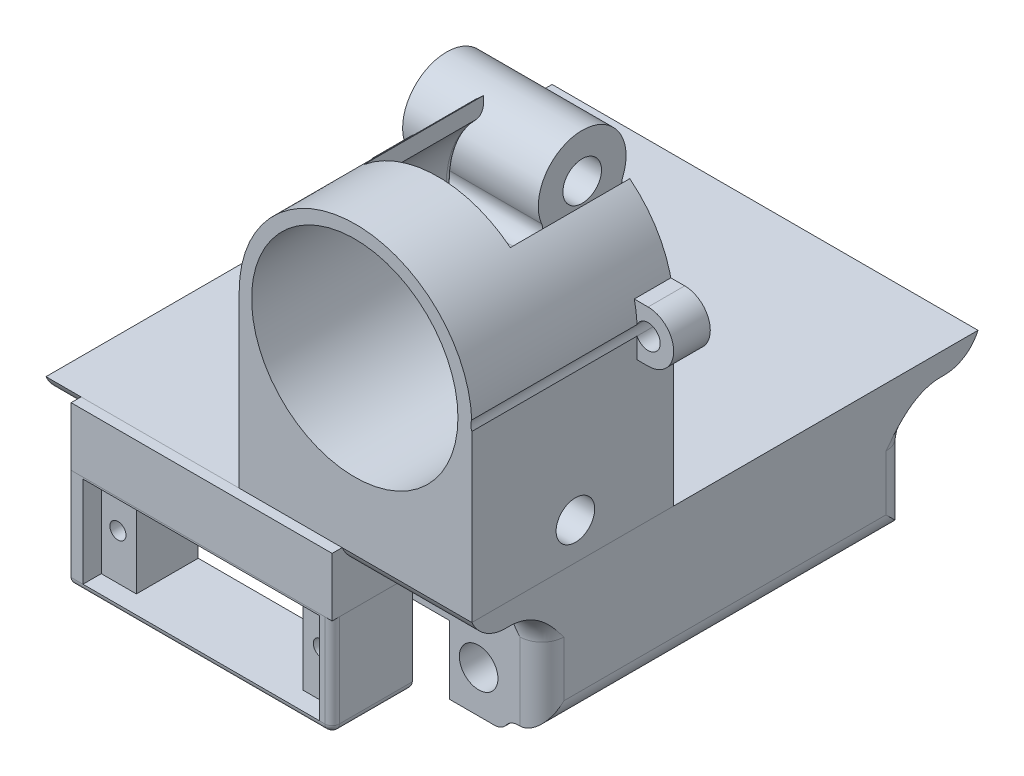
SolidWorks part; units mm, degrees
material "PLA"
ref_plane "Front Plane" through (0, 0, 0) normal (0, 0, 1) x (1, 0, 0)
ref_plane "Top Plane" through (0, 0, 0) normal (0, 1, 0) x (1, 0, 0)
ref_plane "Right Plane" through (0, 0, 0) normal (1, 0, 0) x (0, 0, -1)
ref_plane "Plane69" through (0, 0, 32) normal (0, 0, -1) x (-1, 0, 0)
sketch "Sketch1047" plane through (0, 0, 32) normal (0, 0, -1) x (-1, 0, 0)
  line L0 (-99.3586, 143.8623) -> (-99.3586, 121.2496)
  line L1 (-99.3586, 121.2496) -> (-67.5672, 121.2496)
  line L2 (-67.5672, 121.2496) -> (-67.5672, 144.5496)
  arc A0 (-67.5672, 144.5496) -> (-99.3451, 145.2066) centre (-83.4629, 144.5496) ccw
  arc A1 (-99.3451, 145.2066) -> (-99.3586, 143.8623) centre (-100.8586, 144.5496) cw
extrude "Boss-Extrude62" add sketch "Sketch1047" against normal blind 27.5826 separate body
sketch "Sketch1048" plane through (0, 0, 32) normal (0, 0, -1) x (-1, 0, 0)
  line L0 (-93.3586, 156.9894) -> (-93.3586, 154.49)
  line L1 (-73.3586, 154.49) -> (-73.3586, 156.8206)
  arc A0 (-73.3586, 156.8206) -> (-93.3586, 156.9894) centre (-83.4629, 144.5496) ccw
  arc A1 (-93.3586, 154.49) -> (-73.3586, 154.49) centre (-83.3586, 144.5496) cw
extrude "Cut-Extrude69" cut sketch "Sketch1048" against normal blind 16.3164
ref_plane "Plane70" through (0, 144.5496, 0) normal (0, 1, 0) x (1, 0, 0)
sketch "Sketch1053" plane through (0, 144.5496, 0) normal (0, 1, 0) x (1, 0, 0)
  line L0 (97.4586, -32) -> (83.3586, -32)
  line L1 (83.3586, -32) -> (83.3586, -59.5826)
  line L2 (83.3586, -59.5826) -> (97.4586, -59.5826)
  line L3 (97.4586, -59.5826) -> (97.4586, -32)
  line L4 (83.3586, -32) -> (83.3586, -59.5826) construction
revolve "Cut-Revolve3" cut sketch "Sketch1053" angle 360 about L1 reverse direction yes
hole_wizard "Hole28" positions "Sketch1055" profile "Sketch1054" legacy
sketch "Sketch1055" plane through (99.3586, 0, 0) normal (1, 0, 0) x (0, 0, -1)
  point P0 (-45.4327, 126.3054)
sketch "Sketch1054" plane through (99.3586, 126.3054, 45.4327) normal (0, 1, 0) x (0, 0, -1)
  line L0 (0, 0) -> (0, 31.7914)
  line L1 (0, 31.7914) -> (2.6375, 31.7914)
  line L2 (2.6375, 31.7914) -> (2.6375, 0)
  line L3 (2.6375, 0) -> (0, 0)
  line L4 (0, 110) -> (0, -10) construction
  dimension "Diameter" = 5.275
  dimension "Depth" = 31.7914
fillet "Fillet36" radius 1 1 edges at (83.3586, 130.4496, 32) tangent propagation no
ref_plane "Plane71" through (96.091, 0, 0) normal (1, 0, 0) x (0, 0, -1)
sketch "Sketch1061" plane through (96.091, 0, 0) normal (1, 0, 0) x (0, 0, -1)
  line L0 (-55, 118.2496) -> (5, 118.2496)
  line L1 (9.5826, 121.2496) -> (-59.5826, 121.2496)
  arc A0 (-59.5826, 121.2496) -> (-55, 118.2496) centre (-55, 123.2496) ccw
  arc A1 (5, 118.2496) -> (9.5826, 121.2496) centre (5, 123.2496) ccw
extrude "Boss-Extrude63" add sketch "Sketch1061" against normal blind 3.2327 separate body
ref_plane "Plane72" through (0, 0, -5) normal (0, 0, -1) x (-1, 0, 0)
sketch "Sketch1068" plane through (0, 0, -5) normal (0, 0, -1) x (-1, 0, 0)
  line L0 (-92.8583, 101.0527) -> (-92.8583, 118.2496)
  line L1 (-92.8583, 118.2496) -> (-96.091, 118.2496)
  line L2 (-96.091, 118.2496) -> (-96.091, 102.6969)
  arc A0 (-96.091, 102.6969) -> (-94.4746, 101.8748) centre (-96.091, 100.6969) cw
  arc A1 (-94.4746, 101.8748) -> (-92.8583, 101.0527) centre (-92.8583, 103.0527) ccw
extrude "Boss-Extrude64" add sketch "Sketch1068" against normal blind 60
ref_plane "Plane73" through (92.8583, 0, 0) normal (-1, 0, 0) x (0, 0, 1)
sketch "Sketch1076" plane through (92.8583, 0, 0) normal (-1, 0, 0) x (0, 0, 1)
  line L0 (-5, 101.0527) -> (-5, 118.2496)
  line L1 (-9.5826, 121.2496) -> (59.5826, 121.2496)
  line L2 (55, 118.2496) -> (55, 101.0527)
  line L3 (55, 101.0527) -> (-5, 101.0527)
  arc A0 (-5, 118.2496) -> (-9.5826, 121.2496) centre (-5, 123.2496) cw
  arc A1 (59.5826, 121.2496) -> (55, 118.2496) centre (55, 123.2496) cw
extrude "Boss-Extrude65" add sketch "Sketch1076" along normal blind 51.6948
sketch "Sketch1077" plane through (41.1635, 0, 0) normal (-1, 0, 0) x (0, 0, 1)
  line L0 (55, 110.3759) -> (-5, 110.3759)
  line L1 (-5, 110.3759) -> (-5, 101.0527)
  line L2 (-5, 101.0527) -> (55, 101.0527)
  line L3 (55, 101.0527) -> (55, 110.3759)
extrude "Cut-Extrude70" cut sketch "Sketch1077" against normal blind 45.5365
sketch "Sketch1078" plane through (96.091, 0, 0) normal (1, 0, 0) x (0, 0, -1)
  line L0 (5, 118.2496) -> (5, 102.6969)
  line L1 (5, 102.6969) -> (-55, 102.6969)
  line L2 (-55, 102.6969) -> (-55, 118.2496)
  line L3 (-59.5826, 121.2496) -> (9.5826, 121.2496)
  arc A0 (-55, 118.2496) -> (-59.5826, 121.2496) centre (-55, 123.2496) cw
  arc A1 (9.5826, 121.2496) -> (5, 118.2496) centre (5, 123.2496) cw
extrude "Boss-Extrude66" add sketch "Sketch1078" along normal blind 3.2677
ref_plane "Plane74" through (0, 0, 45) normal (0, 0, 1) x (1, 0, 0)
sketch "Sketch1087" plane through (0, 0, 45) normal (0, 0, 1) x (1, 0, 0)
  line L0 (96.1422, 102.6969) -> (96.1422, 110.3759)
  line L1 (96.1422, 110.3759) -> (86.7, 110.3759)
  line L2 (86.7, 110.3759) -> (86.7, 101.0527)
  line L3 (86.7, 101.0527) -> (92.8583, 101.0527)
  line L4 (96.091, 102.6969) -> (96.1422, 102.6969)
  arc A0 (92.8583, 101.0527) -> (94.4746, 101.8748) centre (92.8583, 103.0527) ccw
  arc A1 (94.4746, 101.8748) -> (96.091, 102.6969) centre (96.091, 100.6969) cw
extrude "Cut-Extrude71" cut sketch "Sketch1087" against normal blind 40
sketch "Sketch1088" plane through (0, 0, 55) normal (0, 0, 1) x (1, 0, 0)
  line L0 (41.1635, 118.2496) -> (41.1635, 110.3759)
  line L1 (41.1635, 110.3759) -> (86.7, 110.3759)
  line L2 (86.7, 110.3759) -> (86.7, 101.0527)
  line L3 (86.7, 101.0527) -> (92.8583, 101.0527)
  line L4 (96.091, 102.6969) -> (99.3586, 102.6969)
  line L5 (99.3586, 102.6969) -> (99.3586, 118.2496)
  line L6 (99.3586, 118.2496) -> (41.1635, 118.2496)
  arc A0 (92.8583, 101.0527) -> (94.4746, 101.8748) centre (92.8583, 103.0527) ccw
  arc A1 (94.4746, 101.8748) -> (96.091, 102.6969) centre (96.091, 100.6969) cw
extrude "Cut-Extrude72" cut sketch "Sketch1088" against normal blind 5
sketch "Sketch1089" plane through (0, 0, -5) normal (0, 0, -1) x (-1, 0, 0)
  line L0 (-86.7, 110.3759) -> (-41.1635, 110.3759)
  line L1 (-41.1635, 110.3759) -> (-41.1635, 118.2496)
  line L2 (-41.1635, 118.2496) -> (-99.3586, 118.2496)
  line L3 (-99.3586, 118.2496) -> (-99.3586, 102.6969)
  line L4 (-99.3586, 102.6969) -> (-96.091, 102.6969)
  line L5 (-92.8583, 101.0527) -> (-86.7, 101.0527)
  line L6 (-86.7, 101.0527) -> (-86.7, 110.3759)
  arc A0 (-96.091, 102.6969) -> (-94.4746, 101.8748) centre (-96.091, 100.6969) cw
  arc A1 (-94.4746, 101.8748) -> (-92.8583, 101.0527) centre (-92.8583, 103.0527) ccw
extrude "Cut-Extrude73" cut sketch "Sketch1089" against normal blind 5
ref_plane "Plane75" through (0, 110.3759, 0) normal (0, -1, 0) x (-1, 0, 0)
sketch "Sketch1099" plane through (0, 110.3759, 0) normal (0, -1, 0) x (-1, 0, 0)
  line L0 (-94.1229, -37) -> (-96.1422, -37)
  line L1 (-96.1422, -37) -> (-96.1422, -13)
  line L2 (-96.1422, -13) -> (-94.1229, -13)
  line L3 (-94.1229, -13) -> (-94.1229, -37)
extrude "Boss-Extrude67" add sketch "Sketch1099" along normal blind 7.679 separate body
sketch "Sketch1110" plane through (0, 110.3759, 0) normal (0, -1, 0) x (-1, 0, 0)
  line L0 (-96.1422, -13) -> (-85.1422, -13)
  line L1 (-85.1422, -13) -> (-85.1422, -5)
  line L2 (-85.1422, -5) -> (-96.1422, -5)
  line L3 (-96.1422, -5) -> (-96.1422, -13)
extrude "Cut-Extrude74" cut sketch "Sketch1110" against normal blind 7.321
sketch "Sketch1111" plane through (0, 110.3759, 0) normal (0, -1, 0) x (1, 0, 0)
  line L0 (96.1422, 37) -> (96.1422, 45)
  line L1 (96.1422, 45) -> (85.1422, 45)
  line L2 (85.1422, 45) -> (85.1422, 37)
  line L3 (85.1422, 37) -> (96.1422, 37)
extrude "Cut-Extrude75" cut sketch "Sketch1111" against normal blind 7.321
ref_plane "Plane76" through (41.1635, 0, 0) normal (-1, 0, 0) x (0, 0, 1)
sketch "Sketch1122" plane through (41.1635, 0, 0) normal (-1, 0, 0) x (0, 0, 1)
  line L0 (-2.5433, 121.2496) -> (12.2435, 121.2496)
  arc A0 (-0.6949, 124.0136) -> (-2.5433, 121.2496) centre (-2.5433, 123.2496) cw
  arc A1 (12.2435, 121.2496) -> (10.3952, 124.0136) centre (12.2435, 123.2496) cw
  arc A2 (10.3952, 124.0136) -> (-0.6949, 124.0136) centre (4.8501, 126.3054) ccw
extrude "Boss-Extrude68" add sketch "Sketch1122" against normal blind 18.5396
sketch "Sketch1133" plane through (0, 110.3759, 0) normal (0, -1, 0) x (-1, 0, 0)
  line L0 (-59.7031, 0) -> (-41.1635, 0)
  line L1 (-41.1635, 0) -> (-41.1635, -5)
  line L2 (-41.1635, -5) -> (-59.7031, -5)
  line L3 (-59.7031, -5) -> (-59.7031, 0)
extrude "Boss-Extrude69" add sketch "Sketch1133" along normal blind 12.0309
ref_plane "Plane77" through (0, 115.3759, 0) normal (0, 1, 0) x (1, 0, 0)
sketch "Sketch1145" plane through (0, 115.3759, 0) normal (0, 1, 0) x (1, 0, 0)
  line L0 (56.7641, -5) -> (41.1635, -5)
  line L1 (41.1635, -5) -> (41.1635, -17)
  line L2 (41.1635, -17) -> (56.7641, -17)
  line L3 (56.7641, -17) -> (56.7641, -5)
extrude "Cut-Extrude76" cut sketch "Sketch1145" against normal up to surface (5 mm away) up to plane "Plane75"
sketch "Sketch1156" plane through (0, 110.3759, 0) normal (0, -1, 0) x (1, 0, 0)
  line L0 (73.7751, 27) -> (63.2027, 27)
  line L1 (63.2027, 27) -> (63.2027, 33)
  line L2 (63.2027, 33) -> (73.7751, 33)
  line L3 (73.7751, 33) -> (73.7751, 27)
extrude "Boss-Extrude70" add sketch "Sketch1156" along normal blind 10.733
sketch "Sketch1168" plane through (41.1635, 0, 0) normal (-1, 0, 0) x (0, 0, 1)
  line L0 (23, 98.3759) -> (23, 110.3759)
  line L1 (23, 110.3759) -> (17, 110.3759)
  line L2 (17, 110.3759) -> (17, 98.3759)
  line L3 (17, 98.3759) -> (23, 98.3759)
extrude "Boss-Extrude71" add sketch "Sketch1168" against normal blind 15.6006
ref_plane "Plane78" through (63.2027, 0, 0) normal (-1, 0, 0) x (0, 0, 1)
sketch "Sketch1181" plane through (63.2027, 0, 0) normal (-1, 0, 0) x (0, 0, 1)
  line L0 (45, 110.3759) -> (45, 115.3759)
  line L1 (45, 115.3759) -> (33, 115.3759)
  line L2 (33, 115.3759) -> (33, 110.3759)
  line L3 (33, 110.3759) -> (45, 110.3759)
extrude "Cut-Extrude77" cut sketch "Sketch1181" against normal blind 10.5723
ref_plane "Plane79" through (0, 0, 0) normal (0, 0, -1) x (-1, 0, 0)
sketch "Sketch1195" plane through (0, 0, 0) normal (0, 0, -1) x (-1, 0, 0)
  line L0 (-51.329, 98.3451) -> (-50.1993, 98.3451)
  arc A0 (-50.1993, 98.3451) -> (-51.329, 98.3451) centre (-50.7641, 97.4012) ccw
extrude "Cut-Extrude78" cut sketch "Sketch1195" against normal blind 3
hole_wizard "Hole29" positions "Sketch1197" profile "Sketch1196" legacy
sketch "Sketch1197" plane through (41.1635, 0, 0) normal (-1, 0, 0) x (0, 0, 1)
  point P0 (4.8501, 126.3054)
sketch "Sketch1196" plane through (41.1635, 126.3054, 4.8501) normal (0, 1, 0) x (0, 0, 1)
  line L0 (0, 0) -> (0, 58.1952)
  line L1 (0, 58.1952) -> (2.6375, 58.1952)
  line L2 (2.6375, 58.1952) -> (2.6375, 0)
  line L3 (2.6375, 0) -> (0, 0)
  line L4 (0, 110) -> (0, -10) construction
  dimension "Diameter" = 5.275
  dimension "Depth" = 58.1952
hole_wizard "Hole30" positions "Sketch1199" profile "Sketch1198" legacy
sketch "Sketch1199" plane through (0, 0, 5) normal (0, 0, 1) x (1, 0, 0)
  point P0 (90.7, 106.8021)
  point P1 (50.7641, 106.1512)
sketch "Sketch1198" plane through (90.7, 106.8021, 5) normal (1, 0, 0) x (0, -1, 0)
  line L0 (0, 0) -> (0, 14.5826)
  line L1 (0, 14.5826) -> (2.6375, 14.5826)
  line L2 (2.6375, 14.5826) -> (2.6375, 0)
  line L3 (2.6375, 0) -> (0, 0)
  line L4 (0, 110) -> (0, -10) construction
  dimension "Diameter" = 5.275
  dimension "Depth" = 14.5826
hole_wizard "Hole31" positions "Sketch1201" profile "Sketch1200" legacy
sketch "Sketch1201" plane through (0, 0, 50) normal (0, 0, 1) x (1, 0, 0)
  point P0 (90.7, 106.8021)
sketch "Sketch1200" plane through (90.7, 106.8021, 50) normal (1, 0, 0) x (0, -1, 0)
  line L0 (0, 0) -> (0, 59.5826)
  line L1 (0, 59.5826) -> (2.6375, 59.5826)
  line L2 (2.6375, 59.5826) -> (2.6375, 0)
  line L3 (2.6375, 0) -> (0, 0)
  line L4 (0, 110) -> (0, -10) construction
  dimension "Diameter" = 5.275
  dimension "Depth" = 59.5826
hole_wizard "Hole32" positions "Sketch1203" profile "Sketch1202" legacy
sketch "Sketch1203" plane through (0, 0, 23) normal (0, 0, 1) x (1, 0, 0)
  point P0 (50.7641, 106.1512)
sketch "Sketch1202" plane through (50.7641, 106.1512, 23) normal (1, 0, 0) x (0, -1, 0)
  line L0 (0, 0) -> (0, 32.5826)
  line L1 (0, 32.5826) -> (2.6375, 32.5826)
  line L2 (2.6375, 32.5826) -> (2.6375, 0)
  line L3 (2.6375, 0) -> (0, 0)
  line L4 (0, 110) -> (0, -10) construction
  dimension "Diameter" = 5.275
  dimension "Depth" = 32.5826
hole_wizard "Hole33" positions "Sketch1205" profile "Sketch1204" legacy
sketch "Sketch1205" plane through (0, 0, 27) normal (0, 0, -1) x (-1, 0, 0)
  point P0 (-68.9089, 106.8021)
sketch "Sketch1204" plane through (68.9089, 106.8021, 27) normal (1, 0, 0) x (0, 1, 0)
  line L0 (0, 0) -> (0, 32.5827)
  line L1 (0, 32.5827) -> (2.6375, 32.5827)
  line L2 (2.6375, 32.5827) -> (2.6375, 0)
  line L3 (2.6375, 0) -> (0, 0)
  line L4 (0, 110) -> (0, -10) construction
  dimension "Diameter" = 5.275
  dimension "Depth" = 32.5827
fillet "Fillet37" radius 1 1 edges at (55.516, 98.3451, 0) tangent propagation no
fillet "Fillet38" radius 2 1 edges at (48.9638, 110.3759, 23)
fillet "Fillet39" radius 2 1 edges at (56.7641, 110.3759, 21)
fillet "Fillet40" radius 3 3 edges at (99.3586, 110.4733, 50) (99.3586, 110.4733, 0) (99.3586, 102.6969, 25)
fillet "Fillet41" radius 5 2 edges at (98.48, 118.2496, 49.1213) (98.48, 118.2496, 0.8787) tangent propagation no
ref_plane "Plane80" through (81.6304, 0, 0) normal (1, 0, 0) x (0, 0, -1)
sketch "Sketch1220" plane through (81.6304, 0, 0) normal (1, 0, 0) x (0, 0, -1)
  line L0 (-60.95, 113.2496) -> (-50, 113.2496)
  line L1 (-59.5826, 121.2496) -> (-60.95, 121.2496)
  line L2 (-60.95, 121.2496) -> (-60.95, 113.2496)
  arc A0 (-50, 113.2496) -> (-55, 118.2496) centre (-55, 113.2496) ccw
  arc A1 (-55, 118.2496) -> (-59.5826, 121.2496) centre (-55, 123.2496) cw
extrude "Boss-Extrude72" add sketch "Sketch1220" against normal blind 35.6727 separate body
ref_plane "Plane81" through (0, 0, 37) normal (0, 0, 1) x (1, 0, 0)
sketch "Sketch1236" plane through (0, 0, 37) normal (0, 0, 1) x (1, 0, 0)
  line L0 (100.8586, 148.0496) -> (98.9685, 148.0496)
  line L1 (99.3586, 143.8623) -> (99.3586, 141.0496)
  line L2 (99.3586, 141.0496) -> (100.8586, 141.0496)
  arc A0 (98.9685, 148.0496) -> (99.3451, 145.2066) centre (83.4629, 144.5496) cw
  arc A1 (99.3451, 145.2066) -> (99.3586, 143.8623) centre (100.8586, 144.5496) cw
  arc A2 (100.8586, 141.0496) -> (100.8586, 148.0496) centre (100.8586, 144.5496) ccw
  arc A3 (99.3451, 145.2066) -> (67.5672, 144.5496) centre (83.4629, 144.5496) ccw construction
extrude "Boss-Extrude73" add sketch "Sketch1236" against normal blind 5 separate body
ref_plane "Plane82" through (0, 0, 60.95) normal (0, 0, 1) x (1, 0, 0)
sketch "Sketch1253" plane through (0, 0, 60.95) normal (0, 0, 1) x (1, 0, 0)
  line L0 (81.6304, 99.5722) -> (81.6304, 113.2496)
  line L1 (81.6304, 113.2496) -> (45.9576, 113.2496)
  line L2 (45.9576, 113.2496) -> (45.9576, 99.5722)
  line L3 (45.9576, 99.5722) -> (81.6304, 99.5722)
extrude "Boss-Extrude74" add sketch "Sketch1253" against normal blind 10.95 separate body
sketch "Sketch1254" plane through (0, 0, 50) normal (0, 0, -1) x (-1, 0, 0)
  line L0 (-52.3839, 113.0271) -> (-75.1339, 113.0271)
  line L1 (-75.1339, 113.0271) -> (-75.1339, 100.5771)
  line L2 (-75.1339, 100.5771) -> (-52.3839, 100.5771)
  line L3 (-52.3839, 100.5771) -> (-52.3839, 113.0271)
extrude "Cut-Extrude79" cut sketch "Sketch1254" against normal through all
ref_plane "Plane83" through (0, 0, 58.45) normal (0, 0, -1) x (-1, 0, 0)
sketch "Sketch1272" plane through (0, 0, 58.45) normal (0, 0, -1) x (-1, 0, 0)
  line L0 (-79.9339, 113.0271) -> (-79.9339, 100.5771)
  line L1 (-79.9339, 100.5771) -> (-75.1339, 100.5771)
  line L2 (-75.1339, 100.5771) -> (-75.1339, 113.0271)
  line L3 (-75.1339, 113.0271) -> (-79.9339, 113.0271)
extrude "Cut-Extrude80" cut sketch "Sketch1272" against normal up to surface (2.5 mm away) up to plane "Plane82"
sketch "Sketch1308" plane through (0, 0, 58.45) normal (0, 0, -1) x (-1, 0, 0)
  line L0 (-47.5839, 100.5771) -> (-47.5839, 113.0271)
  line L1 (-47.5839, 113.0271) -> (-52.3839, 113.0271)
  line L2 (-52.3839, 113.0271) -> (-52.3839, 100.5771)
  line L3 (-52.3839, 100.5771) -> (-47.5839, 100.5771)
extrude "Cut-Extrude81" cut sketch "Sketch1308" against normal up to surface (2.5 mm away) up to plane "Plane82"
hole_wizard "Ø2.2 (2.2) Diameter Hole8" positions "Sketch1327" profile "Sketch1326" hole size "Ø2.2" standard "ANSI Metric"
sketch "Sketch1327" plane through (0, 0, 50) normal (0, 0, -1) x (-1, 0, 0)
  point P0 (-49.8589, 106.8021)
  point P1 (-77.6589, 106.8021)
sketch "Sketch1326" plane through (49.8589, 106.8021, 50) normal (1, 0, 0) x (0, 1, 0)
  line L0 (0, 0) -> (0, 10.9501)
  line L1 (0, 10.9501) -> (1.1, 10.9501)
  line L2 (1.1, 10.9501) -> (1.1, 0)
  line L5 (1.1, 0) -> (0, 0)
  line L10 (0, 10.9501) -> (-1.1, 10.9501) construction
  line L11 (0, -6.35) -> (0, 107.95) construction
  dimension "Hole Dia." = 2.2
  dimension "Hole Depth" = 10.9501
  dimension "Drill Angle" = 180
fillet "Fillet42" radius 1 5 edges at (81.6304, 106.4109, 60.95) (63.794, 99.5722, 60.95) (81.6304, 99.5722, 55.475) (63.794, 99.5722, 50) (45.9576, 99.5722, 55.475)
sketch "Sketch1344" plane through (0, 0, 37) normal (0, 0, 1) x (1, 0, 0)
  line L0 (67.9573, 148.0496) -> (65.8586, 148.0496)
  line L1 (65.8586, 141.0496) -> (67.5672, 141.0496)
  line L2 (67.5672, 141.0496) -> (67.5672, 144.5496)
  arc A0 (67.5672, 144.5496) -> (67.9573, 148.0496) centre (83.4629, 144.5496) cw
  arc A1 (65.8586, 148.0496) -> (65.8586, 141.0496) centre (65.8586, 144.5496) ccw
  circle A2 centre (65.8586, 144.5496) radius 1.65
extrude "Boss-Extrude75" add sketch "Sketch1344" against normal blind 5 separate body
